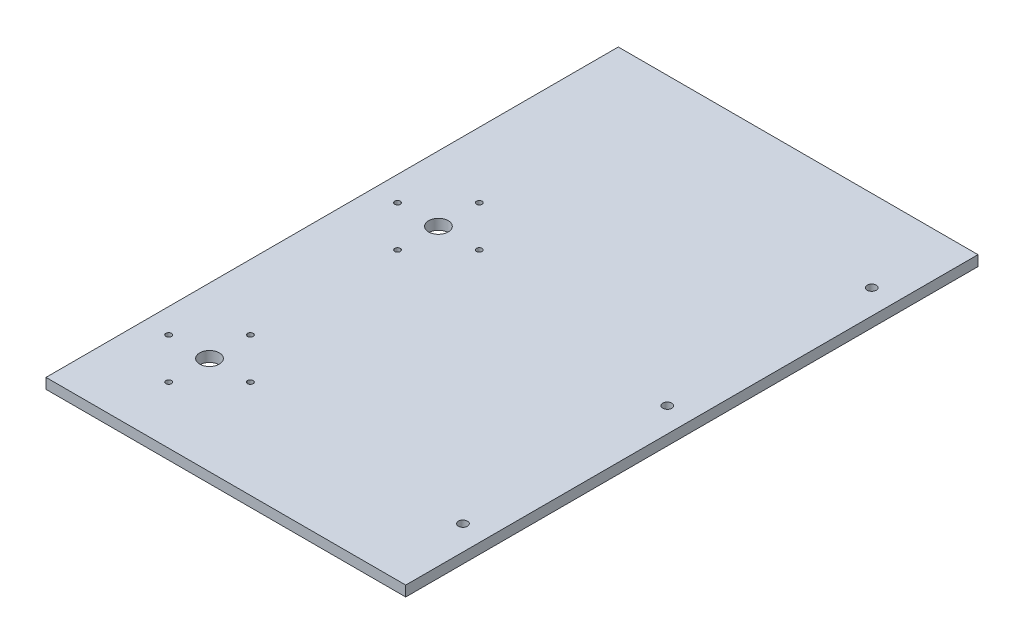
SolidWorks part; units mm, degrees
ref_plane "Front Plane" through (0, 0, 0) normal (0, 0, 1) x (1, 0, 0)
ref_plane "Top Plane" through (0, 0, 0) normal (0, 1, 0) x (1, 0, 0)
ref_plane "Right Plane" through (0, 0, 0) normal (1, 0, 0) x (0, 0, -1)
sketch "Sketch1" plane through (0, 0, 0) normal (0, 1, 0) x (1, 0, 0)
  line L1 (-110, -175) -> (110, -175)
  line L2 (-110, -175) -> (-110, 175)
  line L3 (-110, 175) -> (110, 175)
  line L4 (110, -175) -> (110, 175)
  line L5 (-110, -175) -> (110, 175) construction
  line L6 (-110, 175) -> (110, -175) construction
  point P0 (0, 0)
  dimension "D1" = 350
  dimension "D2" = 220
extrude "Boss-Extrude1" add sketch "Sketch1" along normal blind 6.35
sketch "Sketch2" plane through (0, 6.35, 0) normal (0, 1, 0) x (1, 0, 0)
  line L0 (-70, -175) -> (-70, 175) construction
  line L1 (-110, -175) -> (110, -175) construction
  line L2 (110, 175) -> (-110, 175) construction
  line L3 (-70, -140) -> (-70, -90) construction
  line L4 (-95, -115) -> (-45, -115) construction
  line L5 (-110, 175) -> (-110, -175) construction
  circle A0 centre (-70, -115) radius 6
  circle A1 centre (-70, -90) radius 1.7
  circle A2 centre (-45, -115) radius 1.7
  circle A3 centre (-70, -140) radius 1.7
  circle A4 centre (-95, -115) radius 1.7
  point P11 (-70, -115)
  point P14 (-70, -115)
  dimension "D1" = 12
  dimension "D4" = 60
  dimension "D6" = 3.4
  dimension "D2" = 50
  dimension "D3" = 50
  dimension "D5" = 40
extrude "Cut-Extrude1" cut sketch "Sketch2" against normal through all
sketch "Sketch3" plane through (0, 6.35, 0) normal (0, 1, 0) x (1, 0, 0)
  line L0 (95, -175) -> (95, 175) construction
  line L1 (-110, -175) -> (110, -175) construction
  line L2 (110, 175) -> (-110, 175) construction
  line L3 (110, -175) -> (110, 175) construction
  point P8 (95, 125)
  point P9 (95, 0)
  point P10 (95, -125)
  dimension "D1" = 15
  dimension "D2" = 50
  dimension "D3" = 50
hole_wizard "M5 Clearance Hole1" positions "Sketch4" profile "Sketch5" hole size "M5" standard "ANSI Metric" end condition through all
sketch "Sketch4" plane through (0, 6.35, 0) normal (0, 1, 0) x (1, 0, 0)
  line L0 (95, -175) -> (95, 175) construction
  point P0 (95, -125)
  point P3 (95, 0)
  point P7 (95, 125)
sketch "Sketch5" plane through (95, 6.35, 125) normal (1, 0, 0) x (0, 0, 1)
  line L0 (0, 0) -> (0, 6.35)
  line L1 (0, 6.35) -> (2.75, 6.35)
  line L2 (2.75, 6.35) -> (2.75, 0)
  line L5 (2.75, 0) -> (0, 0)
  line L11 (0, -6.35) -> (0, 107.95) construction
  dimension "Thru Hole Dia." = 5.5
  dimension "Thru Hole Depth" = 6.35
pattern_linear "LPattern1" count 2 spacing 140 along (0, 0, -1) of "Cut-Extrude1"
